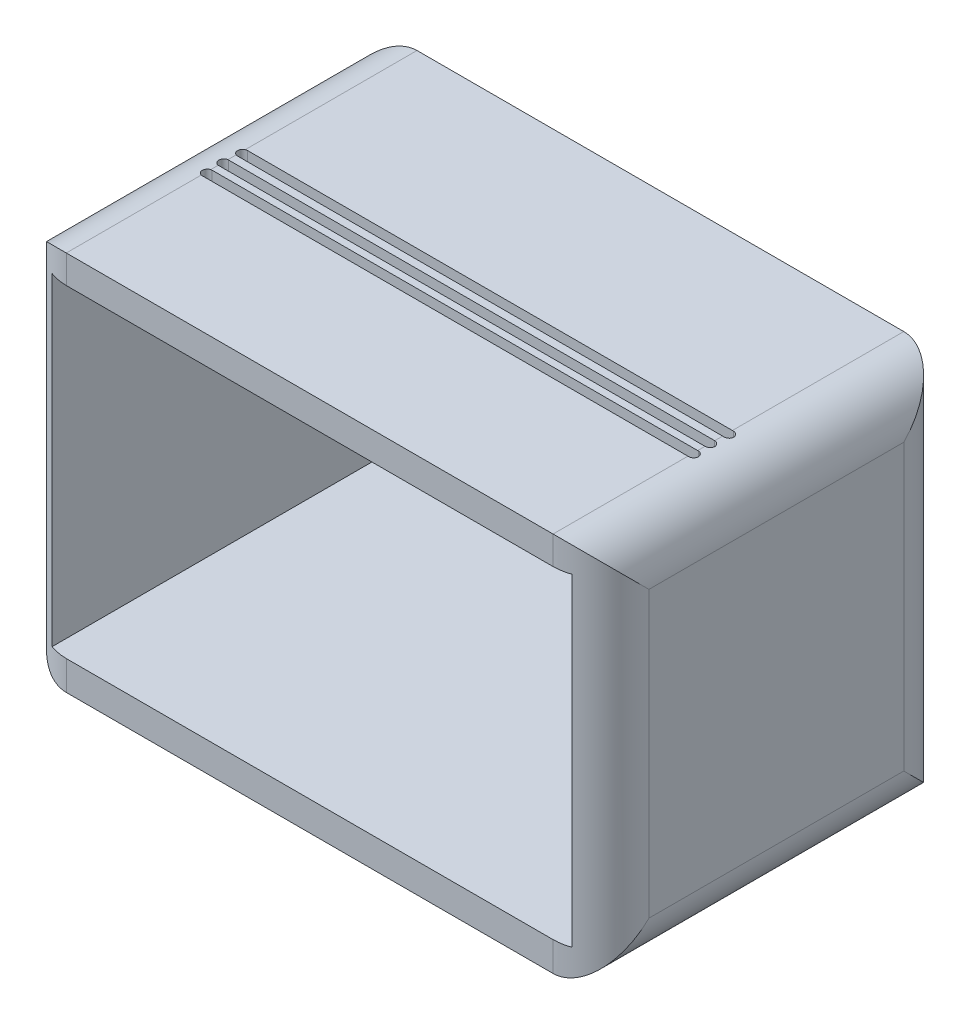
SolidWorks part; units mm, degrees
ref_plane "Ön Düzlem" through (0, 0, 0) normal (0, 0, 1) x (1, 0, 0)
ref_plane "Üst Düzlem" through (0, 0, 0) normal (0, 1, 0) x (1, 0, 0)
ref_plane "Sağ Düzlem" through (0, 0, 0) normal (1, 0, 0) x (0, 0, -1)
sketch "Çizim1" plane through (0, 0, 0) normal (0, 0, 1) x (1, 0, 0)
  line L1 (-50.4208, -30.5103) -> (58.1418, -30.5103)
  line L2 (-50.4208, -30.5103) -> (-50.4208, 36.8819)
  line L3 (-50.4208, 36.8819) -> (58.1418, 36.8819)
  line L4 (58.1418, -30.5103) -> (58.1418, 36.8819)
  line L5 (-56.7925, 42.7634) -> (64.7585, 42.7634)
  line L6 (-56.7925, 42.7634) -> (-56.7925, -36.6368)
  line L7 (-56.7925, -36.6368) -> (64.7585, -36.6368)
  line L8 (64.7585, 42.7634) -> (64.7585, -36.6368)
extrude "Yükseklik-Ekstrüzyon1" add sketch "Çizim1" along normal blind 73.1649
sketch "Çizim2" plane through (0, -30.5103, 0) normal (0, 1, 0) x (1, 0, 0)
  line L1 (58.0412, -0.1373) -> (-50.6245, -0.1373)
  line L2 (58.0412, -0.1373) -> (58.0412, -2.9769)
  line L3 (58.0412, -2.9769) -> (-50.6245, -2.9769)
  line L4 (-50.6245, -0.1373) -> (-50.6245, -2.9769)
extrude "Yükseklik-Ekstrüzyon3" add sketch "Çizim2" along normal blind 67.31
sketch "Çizim4" plane through (0, 0, 0.1373) normal (0, 0, -1) x (-1, 0, 0)
  line L1 (-23.9717, 26.1556) -> (19.7974, 26.1556)
  line L2 (-23.9717, 26.1556) -> (-23.9717, -8.6241)
  line L3 (-23.9717, -8.6241) -> (19.7974, -8.6241)
  line L4 (19.7974, 26.1556) -> (19.7974, -8.6241)
extrude "Kes-Ekstrüzyon3" cut sketch "Çizim4" against normal blind 51.308
fillet "Radyus1" radius 10 4 edges at (64.7585, -36.6368, 36.5825) (64.7585, 3.0633, 73.1649) (64.7585, 42.7634, 36.5825) (64.7585, 3.0633, 0)
fillet "Radyus2" radius 10 4 edges at (-56.7925, 42.7634, 36.5825) (-56.7925, 3.0633, 73.1649) (-56.7925, -36.6368, 36.5825) (-56.7925, 3.0633, 0)
sketch "Çizim5" plane through (0, 42.7634, 0) normal (0, 1, 0) x (1, 0, 0)
  line L7 (-46.4232, -36.769) -> (55.0127, -36.769) construction
  line L8 (-46.4232, -35.752) -> (55.0127, -35.752)
  line L9 (-46.4232, -37.786) -> (55.0127, -37.786)
  line L10 (-46.5504, -44.0153) -> (54.8856, -44.0153) construction
  line L11 (-46.5504, -42.9983) -> (54.8856, -42.9983)
  line L12 (-46.5504, -45.0323) -> (54.8856, -45.0323)
  line L13 (-46.6775, -40.4557) -> (54.7585, -40.4557) construction
  line L14 (-46.6775, -39.4387) -> (54.7585, -39.4387)
  line L15 (-46.6775, -41.4727) -> (54.7585, -41.4727)
  arc A4 (-46.4232, -35.752) -> (-46.4232, -37.786) centre (-46.4232, -36.769) ccw
  arc A5 (55.0127, -37.786) -> (55.0127, -35.752) centre (55.0127, -36.769) ccw
  arc A6 (-46.5504, -42.9983) -> (-46.5504, -45.0323) centre (-46.5504, -44.0153) ccw
  arc A7 (54.8856, -45.0323) -> (54.8856, -42.9983) centre (54.8856, -44.0153) ccw
  arc A8 (-46.6775, -39.4387) -> (-46.6775, -41.4727) centre (-46.6775, -40.4557) ccw
  arc A9 (54.7585, -41.4727) -> (54.7585, -39.4387) centre (54.7585, -40.4557) ccw
  point P18 (4.2948, -36.769)
  point P25 (4.1676, -44.0153)
  point P32 (4.0405, -40.4557)
extrude "Kes-Ekstrüzyon6" cut sketch "Çizim5" against normal blind 25.4
sketch "Çizim6" plane through (0, -36.6368, 0) normal (0, -1, 0) x (-1, 0, 0)
  line L0 (-49.5044, -4.227) -> (-49.5044, -64.0147) construction
  line L1 (-46.871, -4.227) -> (-46.871, -64.0147)
  line L2 (-52.1378, -4.227) -> (-52.1378, -64.0147)
  line L3 (41.6686, -4.5254) -> (41.6686, -64.3132) construction
  line L4 (44.302, -4.5254) -> (44.302, -64.3132)
  line L5 (39.0352, -4.5254) -> (39.0352, -64.3132)
  arc A0 (-46.871, -4.227) -> (-52.1378, -4.227) centre (-49.5044, -4.227) ccw
  arc A1 (-52.1378, -64.0147) -> (-46.871, -64.0147) centre (-49.5044, -64.0147) ccw
  arc A2 (44.302, -4.5254) -> (39.0352, -4.5254) centre (41.6686, -4.5254) ccw
  arc A3 (39.0352, -64.3132) -> (44.302, -64.3132) centre (41.6686, -64.3132) ccw
  point P2 (-49.5044, -34.1209)
  point P9 (41.6686, -34.4193)
extrude "Yükseklik-Ekstrüzyon4" add sketch "Çizim6" along normal blind 4.572
